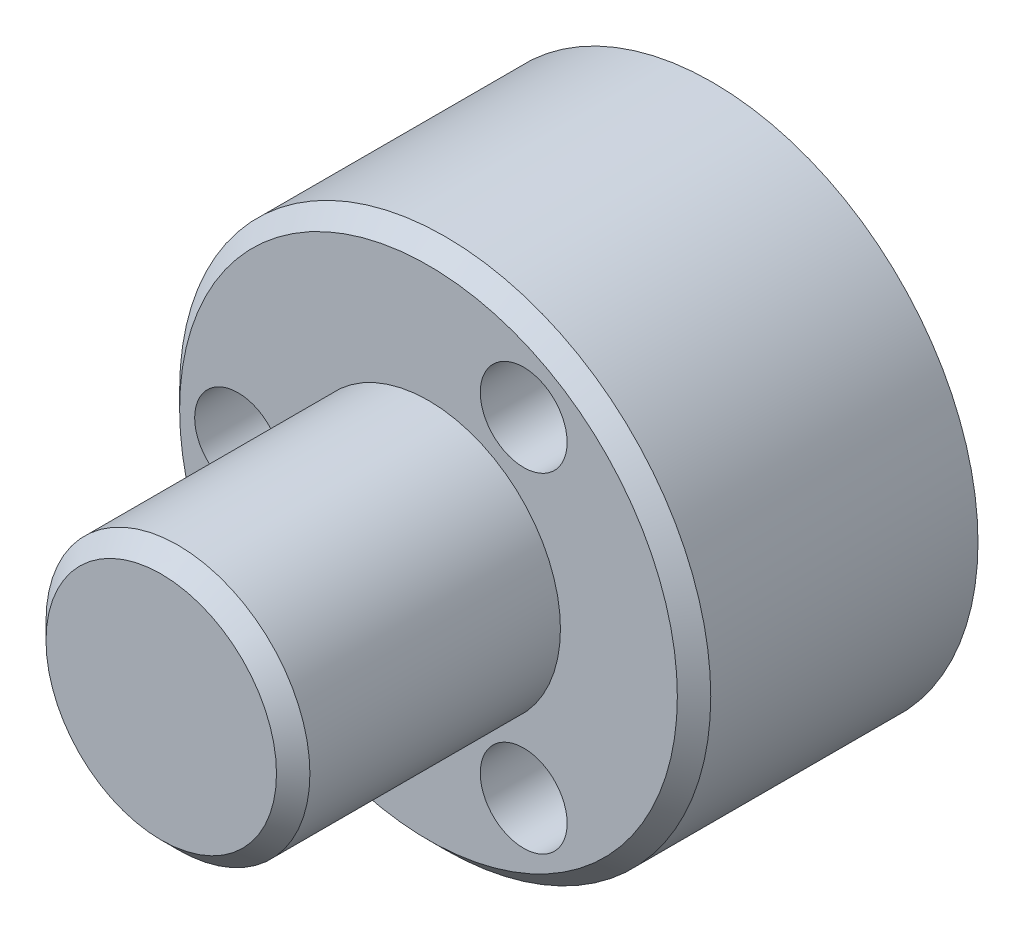
SolidWorks part; units mm, degrees
ref_plane "Front" through (0, 0, 0) normal (0, 0, 1) x (1, 0, 0)
ref_plane "Top" through (0, 0, 0) normal (0, 1, 0) x (1, 0, 0)
ref_plane "Right" through (0, 0, 0) normal (1, 0, 0) x (0, 0, -1)
sketch "Esquisse1" plane through (0, 0, 0) normal (0, 0, 1) x (1, 0, 0)
  circle A0 centre (0, 0) radius 31.25
  dimension "D1" = 62.5
extrude "Boss.-Extru.1" add sketch "Esquisse1" along normal blind 1
sketch "Esquisse2" plane through (0, 0, 1) normal (0, 0, 1) x (1, 0, 0)
  circle A0 centre (0, 0) radius 32.25
  circle A1 centre (0, 0) radius 31.25 construction
  circle A2 centre (0, 0) radius 31.25
  dimension "D1" = 1
extrude "Boss.-Extru.2" add sketch "Esquisse2" along normal blind 25.5 and the other way up to surface (1 mm away) other way up to face at (31.25, 0, 0)
sketch "Esquisse3" plane through (0, 0, 1) normal (0, 0, 1) x (1, 0, 0)
  circle A0 centre (0, 0) radius 7.95
  dimension "D1" = 15.9
extrude "Boss.-Extru.3" add sketch "Esquisse3" along normal blind 7.5
sketch "Esquisse4" plane through (0, 0, 8.5) normal (0, 0, 1) x (1, 0, 0)
  circle A0 centre (0, 0) radius 3.95
  dimension "D1" = 7.9
extrude "Boss.-Extru.4" add sketch "Esquisse4" along normal blind 8
chamfer "Chanfrein1" distance 0.5 angle 45 2 edges at (7.95, 0, 8.5) (3.95, 0, 16.5)
sketch "Esquisse5" plane through (0, 0, 26.5) normal (0, 0, 1) x (1, 0, 0)
  line L0 (-35, 0) -> (0, 0) construction
  arc A0 (-32.0009, -4.0007) -> (-32.0009, 4.0007) centre (-35, 0) cw
  circle A1 centre (0, 0) radius 32.25 construction
  arc A2 (-32.0009, 4.0007) -> (-32.0009, -4.0007) centre (0, 0) ccw
  dimension "D1" = 5
  dimension "D2" = 35
extrude "Boss.-Extru.5" add sketch "Esquisse5" against normal up to surface (26.5 mm away) up to face at (32.25, 0, 0)
sketch "Esquisse6" plane through (0, 0, 26.5) normal (0, 0, 1) x (1, 0, 0)
  circle A0 centre (-35, 0) radius 1.75
  dimension "D1" = 3.5
extrude "Enlèv. mat.-Extru.1" cut sketch "Esquisse6" against normal blind 10
fillet "Congé1" radius 4 2 edges at (-32.0009, 4.0007, 13.25) (-32.0009, -4.0007, 13.25)
pattern_circular "Répétition circulaire2" count 3 over 360 about axis through (0, 0, 26.5) along (0, 0, 1) of "Boss.-Extru.5", "Enlèv. mat.-Extru.1", "Congé1"
sketch "Esquisse7" plane through (0, 0, 26.5) normal (0, 0, 1) x (1, 0, 0)
  arc A12 (-35.064, 4.9996) -> (-35.064, -4.9996) centre (-35, 0) ccw
  arc A13 (-31.2404, -8.0062) -> (-35.064, -4.9996) centre (-35.1152, -8.9993) ccw
  arc A14 (-31.2404, -8.0062) -> (8.6866, -31.0581) centre (0, 0) ccw
  arc A15 (13.2022, -32.8661) -> (8.6866, -31.0581) centre (9.764, -34.9103) ccw
  arc A16 (13.2022, -32.8661) -> (21.8618, -27.8665) centre (17.5, -30.3109) ccw
  arc A17 (22.5538, -23.0519) -> (21.8618, -27.8665) centre (25.3512, -25.911) ccw
  arc A18 (22.5538, -23.0519) -> (22.5538, 23.0519) centre (0, 0) ccw
  arc A19 (21.8618, 27.8665) -> (22.5538, 23.0519) centre (25.3512, 25.911) ccw
  arc A20 (21.8618, 27.8665) -> (13.2022, 32.8661) centre (17.5, 30.3109) ccw
  arc A21 (8.6866, 31.0581) -> (13.2022, 32.8661) centre (9.764, 34.9103) ccw
  arc A22 (8.6866, 31.0581) -> (-31.2404, 8.0062) centre (0, 0) ccw
  arc A23 (-35.064, 4.9996) -> (-31.2404, 8.0062) centre (-35.1152, 8.9993) ccw
  arc A24 (-35.064, 4.9996) -> (-35.064, -4.9996) centre (-35, 0) ccw
  arc A25 (-31.2404, -8.0062) -> (-35.064, -4.9996) centre (-35.1152, -8.9993) ccw
  arc A26 (-31.2404, -8.0062) -> (8.6866, -31.0581) centre (0, 0) ccw
  arc A27 (13.2022, -32.8661) -> (8.6866, -31.0581) centre (9.764, -34.9103) ccw
  arc A28 (13.2022, -32.8661) -> (21.8618, -27.8665) centre (17.5, -30.3109) ccw
  arc A29 (22.5538, -23.0519) -> (21.8618, -27.8665) centre (25.3512, -25.911) ccw
  arc A30 (22.5538, -23.0519) -> (22.5538, 23.0519) centre (0, 0) ccw
  arc A31 (21.8618, 27.8665) -> (22.5538, 23.0519) centre (25.3512, 25.911) ccw
  arc A32 (21.8618, 27.8665) -> (13.2022, 32.8661) centre (17.5, 30.3109) ccw
  arc A33 (8.6866, 31.0581) -> (13.2022, 32.8661) centre (9.764, 34.9103) ccw
  arc A34 (8.6866, 31.0581) -> (-31.2404, 8.0062) centre (0, 0) ccw
  arc A35 (-35.064, 4.9996) -> (-31.2404, 8.0062) centre (-35.1152, 8.9993) ccw
  dimension "D1" = 0
extrude "Enlèv. mat.-Extru.2" [suppressed] cut sketch "Esquisse7" against normal blind 25.5
sketch "Esquisse8" plane through (0, 0, 1) normal (0, 0, 1) x (1, 0, 0)
  circle A0 centre (0, 0) radius 3.95
  dimension "D1" = 7.9
extrude "Boss.-Extru.6" [suppressed] add sketch "Esquisse8" along normal blind 8
sketch "Esquisse9" plane through (0, 0, 1) normal (0, 0, 1) x (1, 0, 0)
  circle A0 centre (-35, 0) radius 2.25
  circle A1 centre (17.5, 30.3109) radius 2.25
  circle A2 centre (17.5, -30.3109) radius 2.25
  dimension "D1" = 4.5
extrude "Enlèv. mat.-Extru.3" [suppressed] cut sketch "Esquisse9" against normal through all
chamfer "Chanfrein2" [suppressed] distance 1 angle 45
sketch "Esquisse10" plane through (0, 0, 1) normal (0, 0, 1) x (1, 0, 0)
  circle A0 centre (0, 0) radius 31
  circle A1 centre (0, 0) radius 27.25
  dimension "D1" = 62
  dimension "D2" = 54.5
extrude "Boss.-Extru.7" [suppressed] add sketch "Esquisse10" along normal blind 0.5
sketch "Esquisse11" [suppressed] plane through (0, 0, 1) normal (0, 0, 1) x (1, 0, 0)
  circle A12 centre (0, 0) radius 31 construction
  circle A13 centre (0, 0) radius 31
  arc A24 (-35.064, 4.9996) -> (-31.2404, 8.0062) centre (-35.1152, 8.9993) ccw
  arc A25 (-35.064, 4.9996) -> (-35.064, -4.9996) centre (-35, 0) ccw
  arc A26 (-31.2404, -8.0062) -> (-35.064, -4.9996) centre (-35.1152, -8.9993) ccw
  arc A27 (-31.2404, -8.0062) -> (8.6866, -31.0581) centre (0, 0) ccw
  arc A28 (13.2022, -32.8661) -> (8.6866, -31.0581) centre (9.764, -34.9103) ccw
  arc A29 (13.2022, -32.8661) -> (21.8618, -27.8665) centre (17.5, -30.3109) ccw
  arc A30 (22.5538, -23.0519) -> (21.8618, -27.8665) centre (25.3512, -25.911) ccw
  arc A31 (22.5538, -23.0519) -> (22.5538, 23.0519) centre (0, 0) ccw
  arc A32 (21.8618, 27.8665) -> (22.5538, 23.0519) centre (25.3512, 25.911) ccw
  arc A33 (21.8618, 27.8665) -> (13.2022, 32.8661) centre (17.5, 30.3109) ccw
  arc A34 (8.6866, 31.0581) -> (13.2022, 32.8661) centre (9.764, 34.9103) ccw
  arc A35 (8.6866, 31.0581) -> (-31.2404, 8.0062) centre (0, 0) ccw
  arc A36 (-35.064, 4.9996) -> (-31.2404, 8.0062) centre (-35.1152, 8.9993) ccw
  arc A37 (-35.064, 4.9996) -> (-35.064, -4.9996) centre (-35, 0) ccw
  arc A38 (-31.2404, -8.0062) -> (-35.064, -4.9996) centre (-35.1152, -8.9993) ccw
  arc A39 (-31.2404, -8.0062) -> (8.6866, -31.0581) centre (0, 0) ccw
  arc A40 (13.2022, -32.8661) -> (8.6866, -31.0581) centre (9.764, -34.9103) ccw
  arc A41 (13.2022, -32.8661) -> (21.8618, -27.8665) centre (17.5, -30.3109) ccw
  arc A42 (22.5538, -23.0519) -> (21.8618, -27.8665) centre (25.3512, -25.911) ccw
  arc A43 (22.5538, -23.0519) -> (22.5538, 23.0519) centre (0, 0) ccw
  arc A44 (21.8618, 27.8665) -> (22.5538, 23.0519) centre (25.3512, 25.911) ccw
  arc A45 (21.8618, 27.8665) -> (13.2022, 32.8661) centre (17.5, 30.3109) ccw
  arc A46 (8.6866, 31.0581) -> (13.2022, 32.8661) centre (9.764, 34.9103) ccw
  arc A47 (8.6866, 31.0581) -> (-31.2404, 8.0062) centre (0, 0) ccw
  dimension "D1" = 0
extrude "Enlèv. mat.-Extru.4" [suppressed] cut sketch "Esquisse11" against normal blind 0.5
sketch "Esquisse12" [suppressed] plane through (0, 0, 0) normal (0, 0, -1) x (-1, 0, 0)
  circle A0 centre (35, 0) radius 2.25 construction
  circle A1 centre (-17.5, -30.3109) radius 2.25 construction
  circle A2 centre (-17.5, 30.3109) radius 2.25 construction
  circle A3 centre (35, 0) radius 2.25
  circle A4 centre (-17.5, -30.3109) radius 2.25
  circle A5 centre (-17.5, 30.3109) radius 2.25
  arc A12 (35.064, -4.9996) -> (35.064, 4.9996) centre (35, 0) ccw
  arc A13 (31.2404, 8.0062) -> (35.064, 4.9996) centre (35.1152, 8.9993) ccw
  arc A14 (31.2404, 8.0062) -> (-8.6866, 31.0581) centre (0, 0) ccw
  arc A15 (-13.2022, 32.8661) -> (-8.6866, 31.0581) centre (-9.764, 34.9103) ccw
  arc A16 (-13.2022, 32.8661) -> (-21.8618, 27.8665) centre (-17.5, 30.3109) ccw
  arc A17 (-22.5538, 23.0519) -> (-21.8618, 27.8665) centre (-25.3512, 25.911) ccw
  arc A18 (-22.5538, 23.0519) -> (-22.5538, -23.0519) centre (0, 0) ccw
  arc A19 (-21.8618, -27.8665) -> (-22.5538, -23.0519) centre (-25.3512, -25.911) ccw
  arc A20 (-21.8618, -27.8665) -> (-13.2022, -32.8661) centre (-17.5, -30.3109) ccw
  arc A21 (-8.6866, -31.0581) -> (-13.2022, -32.8661) centre (-9.764, -34.9103) ccw
  arc A22 (-8.6866, -31.0581) -> (31.2404, -8.0062) centre (0, 0) ccw
  arc A23 (35.064, -4.9996) -> (31.2404, -8.0062) centre (35.1152, -8.9993) ccw
  arc A24 (35.064, -4.9996) -> (35.064, 4.9996) centre (35, 0) ccw
  arc A25 (31.2404, 8.0062) -> (35.064, 4.9996) centre (35.1152, 8.9993) ccw
  arc A26 (31.2404, 8.0062) -> (-8.6866, 31.0581) centre (0, 0) ccw
  arc A27 (-13.2022, 32.8661) -> (-8.6866, 31.0581) centre (-9.764, 34.9103) ccw
  arc A28 (-13.2022, 32.8661) -> (-21.8618, 27.8665) centre (-17.5, 30.3109) ccw
  arc A29 (-22.5538, 23.0519) -> (-21.8618, 27.8665) centre (-25.3512, 25.911) ccw
  arc A30 (-22.5538, 23.0519) -> (-22.5538, -23.0519) centre (0, 0) ccw
  arc A31 (-21.8618, -27.8665) -> (-22.5538, -23.0519) centre (-25.3512, -25.911) ccw
  arc A32 (-21.8618, -27.8665) -> (-13.2022, -32.8661) centre (-17.5, -30.3109) ccw
  arc A33 (-8.6866, -31.0581) -> (-13.2022, -32.8661) centre (-9.764, -34.9103) ccw
  arc A34 (-8.6866, -31.0581) -> (31.2404, -8.0062) centre (0, 0) ccw
  arc A35 (35.064, -4.9996) -> (31.2404, -8.0062) centre (35.1152, -8.9993) ccw
  point P0 (0, 0)
  dimension "D1" = 0
extrude "Boss.-Extru.8" [suppressed] add sketch "Esquisse12" along normal blind 1
sketch "Esquisse13" [suppressed] plane through (0, 0, 1.5) normal (0, 0, 1) x (1, 0, 0)
  line L0 (-14.5625, 25.223) -> (-13.625, 23.5992) construction
  line L1 (-14.5625, 25.223) -> (-15.5, 26.8468) construction
  line L2 (-35, 0) -> (-14.5625, 25.223) construction
  line L3 (-14.5625, 25.223) -> (17.5, 30.3109) construction
  line L4 (-13.625, 23.5992) -> (0, 0) construction
  line L5 (29.125, 0) -> (27.25, 0) construction
  line L6 (29.125, 0) -> (31, 0) construction
  line L7 (-14.5625, -25.223) -> (-13.625, -23.5992) construction
  line L8 (-14.5625, -25.223) -> (-15.5, -26.8468) construction
  circle A0 centre (-14.5625, 25.223) radius 1.25
  circle A1 centre (0, 0) radius 27.25 construction
  circle A2 centre (0, 0) radius 31 construction
  circle A3 centre (29.125, 0) radius 1.25
  circle A4 centre (-14.5625, -25.223) radius 1.25
  point P24 (0, 0)
  dimension "D1" = 2.5
  dimension "D2" = 3
extrude "Enlèv. mat.-Extru.5" [suppressed] cut sketch "Esquisse13" against normal through all
sketch "Esquisse14" plane through (0, 0, 26.5) normal (0, 0, 1) x (1, 0, 0)
  circle A0 centre (0, 0) radius 7.95
  circle A1 centre (0, 0) radius 50
  dimension "D1" = 100
  dimension "D2" = 15.9
extrude "Enlèv. mat.-Extru.6" cut sketch "Esquisse14" against normal through all both and the other way through all
sketch "Esquisse15" plane through (0, 0, 0) normal (0, 0, -1) x (-1, 0, 0)
  line L0 (0, 0) -> (5.7, 0) construction
  circle A0 centre (5.7, 0) radius 1.3
  circle A1 centre (-2.85, -4.9363) radius 1.3
  circle A2 centre (-2.85, 4.9363) radius 1.3
  point P10 (0, 0)
  dimension "D1" = 2.6
  dimension "D2" = 5.7
  dimension "D3" = 3
extrude "Enlèv. mat.-Extru.7" cut sketch "Esquisse15" against normal through all
